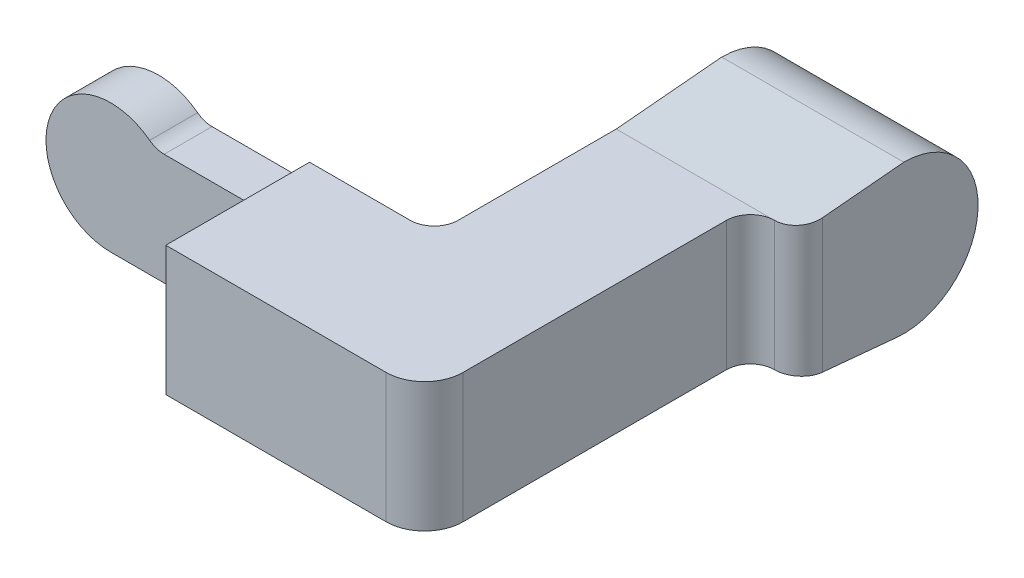
SolidWorks part; units mm, degrees
ref_plane "Front Plane" through (0, 0, 0) normal (0, 0, 1) x (1, 0, 0)
ref_plane "Top Plane" through (0, 0, 0) normal (0, 1, 0) x (1, 0, 0)
ref_plane "Right Plane" through (0, 0, 0) normal (1, 0, 0) x (0, 0, -1)
sketch "Sketch1" plane through (0, 0, 0) normal (0, 1, 0) x (1, 0, 0)
  line L0 (0, 0) -> (46, 0)
  line L1 (54, 8) -> (54, 68)
  line L2 (54, 68) -> (26, 68)
  line L3 (26, 68) -> (26, 35)
  line L4 (21, 30) -> (0, 30)
  line L7 (0, 15) -> (0, 0)
  line L8 (0, 15) -> (0, 30)
  arc A0 (46, 0) -> (54, 8) centre (46, 8) ccw
  arc A1 (21, 30) -> (26, 35) centre (21, 35) ccw
  dimension "D1" = 8
  dimension "D2" = 5
extrude "Boss-Extrude1" add sketch "Sketch1" along normal blind 13.5 and the other way blind 13.5
sketch "Sketch2" plane through (0, 0, 0) normal (0, 0, 1) x (1, 0, 0)
  line L0 (0, -13.5) -> (-31.5, -13.5)
  line L1 (0, -13.5) -> (0, 13.5) construction
  line L2 (0, 9.7599) -> (-20.3468, 9.7599)
  line L3 (0, 9.7599) -> (0, -13.5)
  line L4 (0, 0) -> (-66.0901, 0) construction
  arc A0 (-23.3612, 10.7708) -> (-31.5, -13.5) centre (-31.5, 0) ccw
  arc A1 (-20.3468, 9.7599) -> (-23.3612, 10.7708) centre (-20.3468, 14.7599) cw
  dimension "D1" = 31.5
  dimension "D2" = 5
extrude "Boss-Extrude2" add sketch "Sketch2" along normal blind 10 from offset 30 offset against normal yes
fillet "Fillet3" radius 2 2 edges type face fillet first side face at (-7.63, 9.7599, -23.75) first side face at (-21.5819, -0.5857, -20) second side face at (0, 1.0033, -17.5)
ref_plane "Plane1" through (26, 0, 0) normal (-1, 0, 0) x (0, 0, 1)
sketch "Sketch4" plane through (26, 0, 0) normal (-1, 0, 0) x (0, 0, 1)
  line L0 (-88.5492, -15.4319) -> (-68, -13.5)
  line L1 (-68, -13.5) -> (-68, 13.5)
  line L2 (-68, 13.5) -> (-90, 15.5)
  arc A0 (-87.2049, 15.2459) -> (-88.5492, -15.4319) centre (-90, 0) ccw
extrude "Boss-Extrude3" add sketch "Sketch4" against normal blind 38 contours L2 A0 L0 L1 region at (26, -0.0105, -85.6898)
fillet "Fillet4" radius 5 1 edges type face fillet first side face at (54, -3.375, -23) second side face at (61.5, -3.375, -68)
fillet "Fillet5" radius 5 1 edges at (64, 0, -68) type face fillet first side face at (62.75, 0, -68) second side face at (64, -0.173, -82.6894)
ref_point "Point1"
ref_point "Point2"
ref_axis "Axis1" through (-31.5, 0, -114.5448) along (0, 0, 1)
sketch "Sketch6" plane through (0, 0, -20) normal (0, 0, 1) x (1, 0, 0)
  line L0 (-31.5, 0) -> (-18.3284, 0) construction
ref_axis "Axis2" through (64, 0, -90) along (-1, 0, 0)
ref_plane "Plane2" through (0, 0, -90) normal (0, 0, 1) x (1, 0, 0)
sketch "Sketch8" plane through (0, 0, -90) normal (0, 0, 1) x (1, 0, 0)
  circle A0 centre (-31.5, 0) radius 20.275 construction
